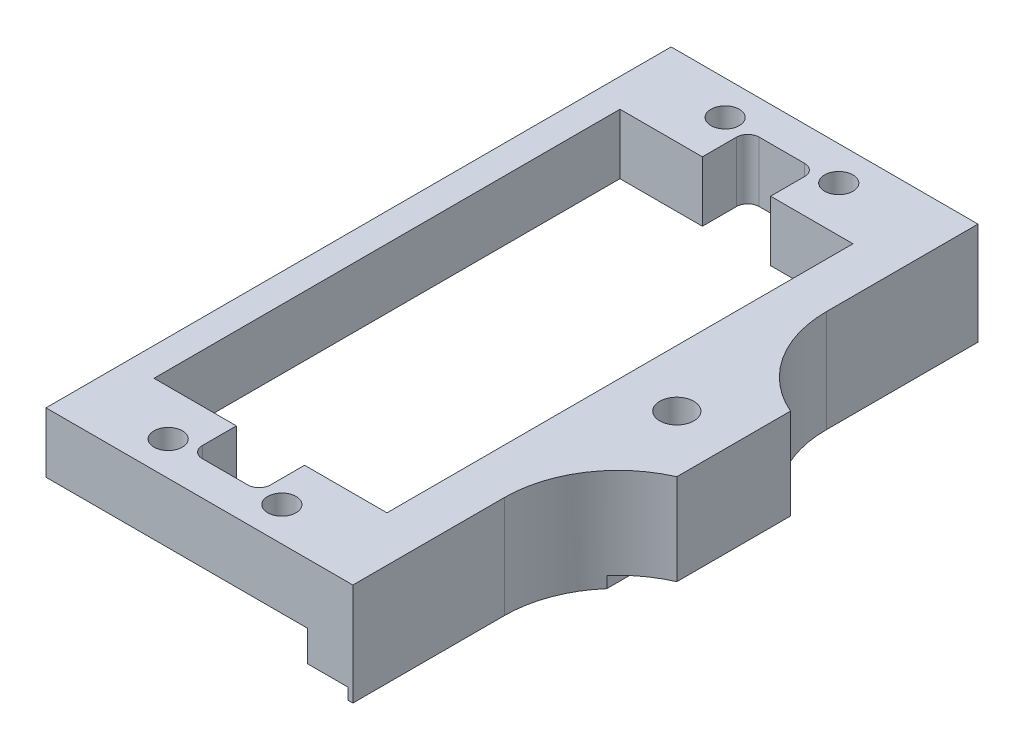
SolidWorks part; units mm, degrees
ref_plane "Front Plane" through (0, 0, 0) normal (0, 0, 1) x (1, 0, 0)
ref_plane "Top Plane" through (0, 0, 0) normal (0, 1, 0) x (1, 0, 0)
ref_plane "Right Plane" through (0, 0, 0) normal (1, 0, 0) x (0, 0, -1)
sketch "Sketch1" plane through (0, 0, 0) normal (0, 0, 1) x (1, 0, 0)
  line L0 (10, 0) -> (10, 8)
  line L1 (10, 8) -> (-23, 8)
  line L2 (-23, 8) -> (-23, 2.7063)
  line L3 (-23, 2.7063) -> (0, 2.7063)
  line L4 (3.55, 0) -> (3.55, -1)
  line L5 (3.55, -1) -> (6.45, -1)
  line L6 (6.45, -1) -> (6.45, 0)
  line L7 (6.45, 0) -> (10, 0)
  line L8 (0, 2.7063) -> (0, 0)
  line L11 (0, 0) -> (3.55, 0)
  dimension "D1" = 10
  dimension "D2" = 1
  dimension "D3" = 8
  dimension "D4" = 2.9
  dimension "D5" = 3.55
  dimension "D6" = 23
extrude "Main" add sketch "Sketch1" along normal mid plane 55
sketch "Sketch3" plane through (0, 8, 0) normal (0, 1, 0) x (1, 0, 0)
  line L0 (-23, -27.5) -> (-23, 27.5) construction
  line L1 (-20.5, 20.5) -> (-13.25, 20.5)
  line L2 (-20.5, 20.5) -> (-20.5, -20.5)
  line L3 (-20.5, -20.5) -> (-13.25, -20.5)
  line L4 (0, 20.5) -> (0, -20.5)
  line L5 (-13.25, 20.5) -> (-13.25, 24.5)
  line L6 (-13.25, 24.5) -> (-7.25, 24.5)
  line L7 (-7.25, 24.5) -> (-7.25, 20.5)
  line L8 (-7.25, 20.5) -> (0, 20.5)
  line L9 (-13.25, -20.5) -> (-13.25, -24.5)
  line L10 (-13.25, -24.5) -> (-7.25, -24.5)
  line L11 (-7.25, -24.5) -> (-7.25, -20.5)
  line L12 (-7.25, -20.5) -> (0, -20.5)
  line L13 (10, -27.5) -> (-23, -27.5) construction
  point P6 (0, 0)
  dimension "D1" = 41
  dimension "D2" = 20.5
  dimension "D3" = 2.5
  dimension "D4" = 6
  dimension "D5" = 4
  dimension "D6" = 3
extrude "ServoSquareHole" cut sketch "Sketch3" against normal through all
sketch "Sketch2" plane through (0, 8, 0) normal (0, 1, 0) x (1, 0, 0)
  line L0 (10, -27.5) -> (10, 27.5) construction
  line L1 (-15.25, -24.5) -> (-15.25, 24.5) construction
  line L2 (-15.25, 24.5) -> (-5.25, 24.5) construction
  line L3 (-7.25, 24.5) -> (-13.25, 24.5) construction
  circle A0 centre (5, 0) radius 1.5
  circle A1 centre (-15.25, 24.5) radius 1.25
  circle A2 centre (-15.25, -24.5) radius 1.25
  circle A3 centre (-5.25, 24.5) radius 1.25
  circle A4 centre (-5.25, -24.5) radius 1.25
  point P9 (-15.25, 0)
  point P15 (-10.25, 24.5)
  dimension "D1" = 3
  dimension "D3" = 2.5
  dimension "D2" = 5
  dimension "D4" = 5
  dimension "D5" = 49
  dimension "D6" = 10
extrude "FixingHole" cut sketch "Sketch2" against normal through all
sketch "Sketch4" plane through (0, 8, 0) normal (0, 1, 0) x (1, 0, 0)
  line L1 (4, 27.5) -> (10, 27.5)
  line L2 (4, 27.5) -> (4, 5)
  line L3 (4, 5) -> (10, 5)
  line L4 (10, 27.5) -> (10, 5)
  line L5 (10, -27.5) -> (10, 27.5) construction
  line L7 (10, -27.5) -> (4, -27.5)
  line L8 (10, -27.5) -> (10, -5)
  line L9 (10, -5) -> (4, -5)
  line L10 (4, -27.5) -> (4, -5)
  line L11 (10, 27.5) -> (-23, 27.5) construction
  dimension "D1" = 10
  dimension "D2" = 6
fillet "Fillet1" radius 1 4 edges at (-7.25, 5.3531, 24.5) (-13.25, 5.3531, 24.5) (-7.25, 5.3531, -24.5) (-13.25, 5.3531, -24.5)
extrude "Cut-Extrude2" cut sketch "Sketch4" against normal through all
fillet "Fillet2" radius 10 2 edges at (4, 3.5, 5) (4, 3.5, -5)
